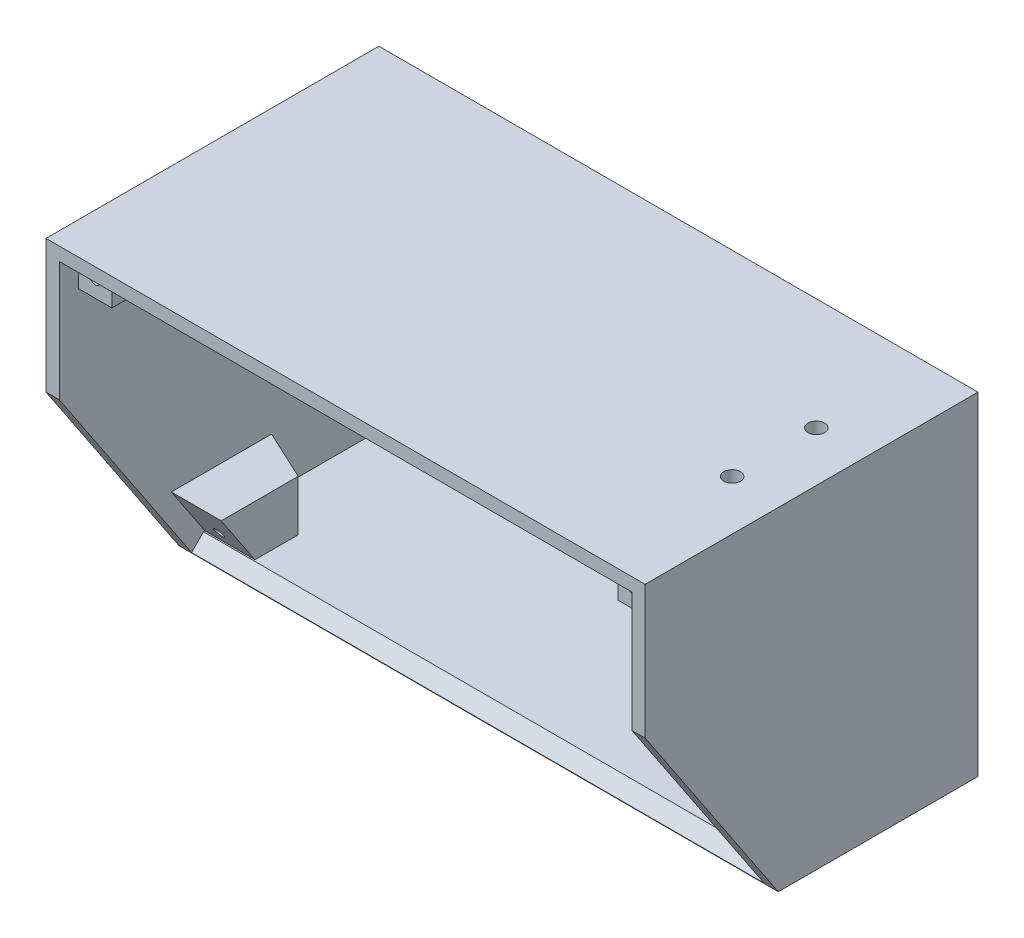
SolidWorks part; units mm, degrees
ref_plane "Plano frontal" through (0, 0, 0) normal (0, 0, 1) x (1, 0, 0)
ref_plane "Plano superior" through (0, 0, 0) normal (0, 1, 0) x (1, 0, 0)
ref_plane "Plano direito" through (0, 0, 0) normal (1, 0, 0) x (0, 0, -1)
sketch "Esboço1" plane through (0, 0, 0) normal (0, 0, 1) x (1, 0, 0)
  line L0 (0, 0) -> (180, 0)
  line L1 (180, 0) -> (180, 100)
  line L2 (180, 100) -> (0, 100)
  line L3 (0, 100) -> (0, 0)
  line L4 (4, 96) -> (4, 4)
  line L5 (4, 4) -> (176, 4)
  line L6 (176, 4) -> (176, 96)
  line L7 (176, 96) -> (4, 96)
extrude "Ressalto-extrusão1" add sketch "Esboço1" along normal blind 100
sketch "Esboço2" plane through (0, 0, 0) normal (0, 0, -1) x (-1, 0, 0)
  line L1 (-180, 100) -> (0, 100)
  line L2 (-180, 100) -> (-180, 0)
  line L3 (-180, 0) -> (0, 0)
  line L4 (0, 100) -> (0, 0)
extrude "Ressalto-extrusão2" add sketch "Esboço2" against normal blind 4
sketch "Esboço3" plane through (0, 0, 4) normal (0, 0, 1) x (1, 0, 0)
  line L0 (30, 96) -> (30, 78)
  line L2 (30, 78) -> (57, 78)
  line L4 (26, 96) -> (26, 74)
  line L5 (154, 96) -> (154, 74)
  line L6 (26, 74) -> (154, 74)
  line L7 (150, 96) -> (150, 78)
  line L8 (57, 96) -> (57, 78)
  line L9 (123, 96) -> (123, 78)
  line L10 (61, 96) -> (61, 78)
  line L11 (119, 96) -> (119, 78)
  line L12 (88, 96) -> (88, 78)
  line L13 (92, 96) -> (92, 78)
  line L14 (61, 78) -> (88, 78)
  line L15 (30, 78) -> (150, 78) construction
  line L16 (92, 78) -> (119, 78)
  line L17 (123, 78) -> (150, 78)
  line L18 (26, 96) -> (30, 96)
  line L19 (57, 96) -> (61, 96)
  line L20 (88, 96) -> (92, 96)
  line L21 (119, 96) -> (123, 96)
  line L22 (150, 96) -> (154, 96)
extrude "Ressalto-extrusão3" add sketch "Esboço3" along normal blind 43
sketch "Esboço4" plane through (0, 0, 0) normal (-1, 0, 0) x (0, 0, 1)
  line L1 (100, 100) -> (100, 0) construction
  line L3 (100, 0) -> (0, 0) construction
  line L4 (60, 0) -> (100, 60)
  line L5 (100, 60) -> (100, 0)
  line L6 (100, 0) -> (60, 0)
extrude "Corte-extrusão1" cut sketch "Esboço4" against normal blind 263
chamfer "Chanfro1" distance 6 angle 45 1 edges at (90, 4, 62.6667) first distance on face at (90, 4, 33.3333)
sketch "Esboço5" plane through (0, 96, 0) normal (0, -1, 0) x (1, 0, 0)
  line L1 (4, 94.2) -> (14, 94.2)
  line L2 (14, 94.2) -> (14, 74.2)
  line L3 (4, 74.2) -> (4, 94.2)
  line L4 (4, 60.2667) -> (4, 100) construction
  line L5 (4, 74.2) -> (14, 74.2)
  line L7 (176, 74.2) -> (166, 74.2)
  line L8 (176, 74.2) -> (176, 94.2)
  line L9 (166, 94.2) -> (166, 74.2)
  line L10 (176, 94.2) -> (166, 94.2)
extrude "Ressalto-extrusão4" add sketch "Esboço5" along normal blind 10
sketch "Esboço6" plane through (0, 0, 94.2) normal (0, 0, 1) x (1, 0, 0)
  circle A0 centre (171, 91) radius 1.5
  circle A1 centre (9, 91) radius 1.5
extrude "Corte-extrusão2" cut sketch "Esboço6" against normal blind 32
sketch "Esboço7" plane through (0, 96, 0) normal (0, -1, 0) x (1, 0, 0)
  circle A0 centre (165, 58.88) radius 2.5
  circle A1 centre (165, 33.58) radius 2.5
extrude "Corte-extrusão3" cut sketch "Esboço7" against normal blind 32
chamfer "Chanfro3" distance 10 angle 25 1 edges at (176, 91, 74.2) first distance on face at (172.5, 91, 74.2)
chamfer "Chanfro4" distance 10 angle 25 1 edges at (4, 91, 74.2) first distance on face at (10.5, 91, 74.2)
sketch "Esboço8" plane through (176, 0, 0) normal (-1, 0, 0) x (0, 0, 1)
  line L2 (95.5402, 62.9732) -> (55.5402, 2.9732)
  line L3 (66.3581, 19.2) -> (56.2247, 4)
  line L4 (56.2247, 4) -> (43.2247, 4)
  line L5 (60, 4) -> (0, 4)
  line L6 (56.2247, 4) -> (43.2247, 4)
  line L7 (43.2247, 4) -> (43.2247, 19.2)
  line L8 (43.2247, 19.2) -> (66.3581, 19.2)
  line M8 (4, 4) -> (56.6667, 4)
  dimension "D1" = 5.36
  dimension "D2" = 4
extrude "Ressalto-extrusão5" add sketch "Esboço8" along normal blind 15 contours L8 L7 L3 M8 region at (176, 12.3105, 52.4949)
sketch "Esboço9" plane through (4, 0, 0) normal (1, 0, 0) x (0, 0, -1)
  line L4 (-43.2247, 19.2) -> (-66.3581, 19.2)
  line L5 (-43.2247, 4) -> (-43.2247, 19.2)
  line L6 (-56.2247, 4) -> (-43.2247, 4)
  line L7 (-66.3581, 19.2) -> (-56.2247, 4)
  line L8 (-43.2247, 19.2) -> (-66.3581, 19.2)
  line L9 (-43.2247, 4) -> (-43.2247, 19.2)
  line L10 (-56.2247, 4) -> (-43.2247, 4)
  line L11 (-66.3581, 19.2) -> (-56.2247, 4)
  dimension "D1" = 0
extrude "Ressalto-extrusão6" add sketch "Esboço9" along normal blind 15
chamfer "Chanfro5" distance 15 angle 25 1 edges at (176, 11.6, 43.2247) first distance on face at (168.5, 11.6, 43.2247)
chamfer "Chanfro6" distance 15 angle 25 1 edges at (4, 11.6, 43.2247) first distance on face at (11.5, 11.6, 43.2247)
sketch "Esboço10" plane through (0, -24.7191, 37.0787) normal (0, -0.5547, 0.8321) x (1, 0, 0)
  circle A0 centre (11.5, 40.3612) radius 1.5
  circle A1 centre (168.5, 40.3756) radius 1.5
extrude "Corte-extrusão4" cut sketch "Esboço10" against normal blind 5
sketch "Esboço11" plane through (0, 0, 4) normal (0, 0, 1) x (1, 0, 0)
  line L1 (117, 52) -> (117, 26)
  line L2 (128, 96) -> (128, 4)
  line L3 (128, 52) -> (128, 26)
  line L4 (92, 52) -> (92, 26)
  line L5 (81, 52) -> (81, 26)
  line L7 (128, 26) -> (117, 26)
  line L8 (176, 52) -> (4, 52)
  line L9 (128, 52) -> (117, 52)
  line L10 (128, 96) -> (128, 4) construction
  line L11 (117, 96) -> (117, 4) construction
  line L12 (92, 96) -> (92, 4) construction
  line L13 (81, 96) -> (81, 4) construction
  line L14 (176, 26) -> (4, 26) construction
  line L15 (176, 52) -> (4, 52) construction
  line L16 (92, 26) -> (81, 26)
  line L17 (92, 52) -> (81, 52)
  circle A0 centre (86.5, 45.5) radius 2
  circle A1 centre (86.5, 32.5) radius 2
  circle A2 centre (122.5, 45.5) radius 2
  circle A3 centre (122.5, 32.5) radius 2
  dimension "D1" = 48
  dimension "D2" = 44
extrude "Ressalto-extrusão7" add sketch "Esboço11" along normal blind 5
